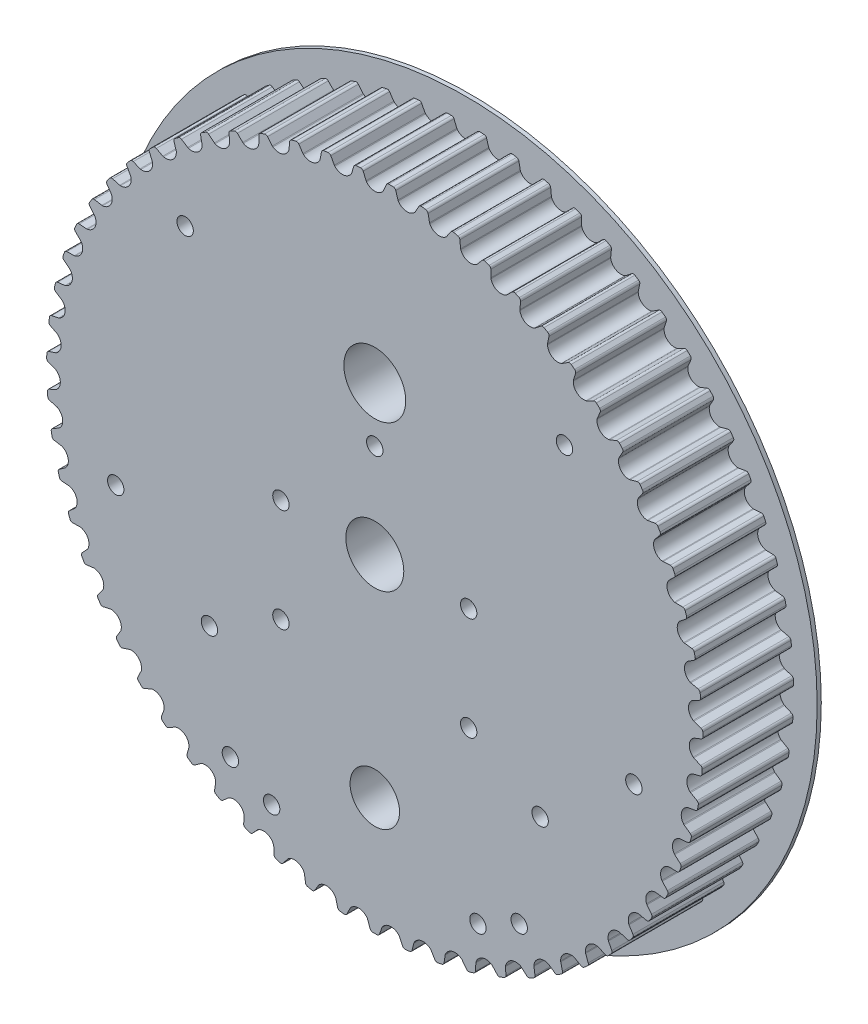
SolidWorks part; units mm, degrees
material "PETG"
ref_plane "Front Plane" through (0, 0, 0) normal (0, 0, 1) x (1, 0, 0)
ref_plane "Top Plane" through (0, 0, 0) normal (0, 1, 0) x (1, 0, 0)
ref_plane "Right Plane" through (0, 0, 0) normal (1, 0, 0) x (0, 0, -1)
sketch "Sketch1" plane through (0, 0, 0) normal (0, 0, 1) x (1, 0, 0)
  line L0 (0, 0) -> (0, 50000) construction
  line L1 (0, 0) -> (3.9983, 80.1144) construction
  line L2 (0, 0) -> (-3.9983, 80.1144) construction
  line L3 (-2.1085, 77.3973) -> (-2.8064, 79.0584)
  line L4 (2.1085, 77.3973) -> (2.8064, 79.0584)
  line L5 (5.6082, 77.2226) -> (5.0793, 78.9449)
  line L6 (9.8043, 76.8027) -> (10.6641, 78.3861)
  line L7 (13.2692, 76.2805) -> (12.9144, 78.0469)
  line L8 (17.4027, 75.4449) -> (18.4158, 76.9348)
  line L9 (20.7984, 74.5802) -> (20.6212, 76.3732)
  line L10 (24.8281, 73.3372) -> (25.9846, 74.7188)
  line L11 (28.1208, 72.1388) -> (28.123, 73.9405)
  line L12 (32.0068, 70.5007) -> (33.295, 71.7603)
  line L13 (35.1638, 68.9804) -> (35.3454, 70.7729)
  line L14 (38.8673, 66.9635) -> (40.2746, 68.0886)
  line L15 (41.8573, 65.1364) -> (42.2164, 66.902)
  line L16 (45.3416, 62.7608) -> (46.8539, 63.7402)
  line L17 (48.1348, 60.6451) -> (48.6679, 62.3661)
  line L18 (51.3652, 57.9344) -> (52.9675, 58.7583)
  line L19 (53.9339, 55.551) -> (54.6358, 57.2105)
  line L20 (56.8784, 52.5322) -> (58.5548, 53.1925)
  line L21 (59.197, 49.9049) -> (60.0606, 51.4862)
  line L22 (61.8263, 46.6079) -> (63.5601, 47.098)
  line L23 (63.8717, 43.7628) -> (64.8885, 45.2502)
  line L24 (66.1597, 40.2204) -> (67.9337, 40.5354)
  line L25 (67.9117, 37.1858) -> (69.0715, 38.5646)
  line L26 (69.8356, 33.4331) -> (71.6321, 33.57)
  line L27 (71.2767, 30.2392) -> (72.5681, 31.4956)
  line L28 (72.8174, 26.3136) -> (74.6186, 26.2709)
  line L29 (73.9334, 22.992) -> (75.3434, 24.1137)
  line L30 (75.0756, 18.9326) -> (76.8636, 18.7107)
  line L31 (75.8553, 15.5164) -> (77.37, 16.4921)
  line L32 (76.5876, 11.3634) -> (78.3446, 10.9646)
  line L33 (77.0233, 7.8865) -> (78.6276, 8.7066)
  line L34 (77.3384, 3.6813) -> (79.047, 3.1095)
  line L35 (77.4258, 0.1783) -> (79.1038, 0.8345)
  line L36 (77.3206, -4.0374) -> (78.9638, -4.7765)
  line L37 (77.0588, -7.5317) -> (78.7938, -7.0458)
  line L38 (76.5344, -11.716) -> (78.0959, -12.615)
  line L39 (75.9259, -15.1668) -> (77.7007, -14.8561)
  line L40 (74.9876, -19.2782) -> (76.4517, -20.3281)
  line L41 (74.0385, -22.6513) -> (75.8354, -22.5188)
  line L42 (72.6954, -26.6487) -> (74.0478, -27.8393)
  line L43 (71.4153, -29.9106) -> (73.2164, -29.9577)
  line L44 (69.6808, -33.7544) -> (70.908, -35.0737)
  line L45 (68.0823, -36.8726) -> (69.8697, -37.0988)
  line L46 (65.9737, -40.5247) -> (67.0634, -41.9596)
  line L47 (64.0726, -43.4682) -> (65.8287, -43.8712)
  line L48 (61.6109, -46.8922) -> (62.5523, -48.4284)
  line L49 (59.4262, -49.6317) -> (61.1334, -50.2076)
  line L50 (56.6358, -52.7936) -> (57.4196, -54.416)
  line L51 (54.1892, -55.302) -> (55.8306, -56.0451)
  line L52 (51.0978, -58.1704) -> (51.7161, -59.8627)
  line L53 (48.4136, -60.4227) -> (49.9728, -61.3255)
  line L54 (45.052, -62.969) -> (45.4988, -64.7145)
  line L55 (42.1568, -64.9429) -> (43.6185, -65.9965)
  line L56 (38.5585, -67.1418) -> (38.8292, -68.9231)
  line L57 (35.4811, -68.8177) -> (36.8306, -70.0115)
  line L58 (31.6817, -70.6474) -> (31.7737, -72.4468)
  line L59 (28.4528, -72.0085) -> (29.6767, -73.3307)
  line L60 (24.49, -73.4508) -> (24.4024, -75.2504)
  line L61 (21.1417, -74.4836) -> (22.2278, -75.9212)
  line L62 (17.055, -75.5242) -> (16.7887, -77.3062)
  line L63 (13.6204, -76.2185) -> (14.5581, -77.7571)
  line L64 (9.4505, -76.8471) -> (9.008, -78.5936)
  line L65 (5.9638, -77.1959) -> (6.7436, -78.8202)
  line L66 (1.752, -77.4061) -> (1.1379, -79.1)
  line L67 (-1.752, -77.4061) -> (-1.1379, -79.1)
  line L68 (-5.9638, -77.1959) -> (-6.7436, -78.8202)
  line L69 (-9.4505, -76.8471) -> (-9.008, -78.5936)
  line L70 (-13.6204, -76.2185) -> (-14.5581, -77.7571)
  line L71 (-17.055, -75.5242) -> (-16.7887, -77.3062)
  line L72 (-21.1417, -74.4836) -> (-22.2278, -75.9212)
  line L73 (-24.49, -73.4508) -> (-24.4024, -75.2504)
  line L74 (-28.4528, -72.0085) -> (-29.6767, -73.3307)
  line L75 (-31.6817, -70.6474) -> (-31.7737, -72.4468)
  line L76 (-35.4811, -68.8177) -> (-36.8306, -70.0115)
  line L77 (-38.5585, -67.1418) -> (-38.8292, -68.9231)
  line L78 (-42.1568, -64.9429) -> (-43.6185, -65.9965)
  line L79 (-45.052, -62.969) -> (-45.4988, -64.7145)
  line L80 (-48.4136, -60.4227) -> (-49.9728, -61.3255)
  line L81 (-51.0978, -58.1704) -> (-51.7161, -59.8627)
  line L82 (-54.1892, -55.302) -> (-55.8306, -56.0451)
  line L83 (-56.6358, -52.7936) -> (-57.4196, -54.416)
  line L84 (-59.4262, -49.6317) -> (-61.1334, -50.2076)
  line L85 (-61.6109, -46.8922) -> (-62.5523, -48.4284)
  line L86 (-64.0726, -43.4682) -> (-65.8287, -43.8712)
  line L87 (-65.9737, -40.5247) -> (-67.0634, -41.9596)
  line L88 (-68.0823, -36.8726) -> (-69.8697, -37.0988)
  line L89 (-69.6808, -33.7544) -> (-70.908, -35.0737)
  line L90 (-71.4153, -29.9106) -> (-73.2164, -29.9577)
  line L91 (-72.6954, -26.6487) -> (-74.0478, -27.8393)
  line L92 (-74.0385, -22.6513) -> (-75.8354, -22.5188)
  line L93 (-74.9876, -19.2782) -> (-76.4517, -20.3281)
  line L94 (-75.9259, -15.1668) -> (-77.7007, -14.8561)
  line L95 (-76.5344, -11.716) -> (-78.0959, -12.615)
  line L96 (-77.0588, -7.5317) -> (-78.7938, -7.0458)
  line L97 (-77.3206, -4.0374) -> (-78.9638, -4.7765)
  line L98 (-77.4258, 0.1783) -> (-79.1038, 0.8345)
  line L99 (-77.3384, 3.6813) -> (-79.047, 3.1095)
  line L100 (-77.0233, 7.8865) -> (-78.6276, 8.7066)
  line L101 (-76.5876, 11.3634) -> (-78.3446, 10.9646)
  line L102 (-75.8553, 15.5164) -> (-77.37, 16.4921)
  line L103 (-75.0756, 18.9326) -> (-76.8636, 18.7107)
  line L104 (-73.9334, 22.992) -> (-75.3434, 24.1137)
  line L105 (-72.8174, 26.3136) -> (-74.6186, 26.2709)
  line L106 (-71.2767, 30.2392) -> (-72.5681, 31.4956)
  line L107 (-69.8356, 33.4331) -> (-71.6321, 33.57)
  line L108 (-67.9117, 37.1858) -> (-69.0715, 38.5646)
  line L109 (-66.1597, 40.2204) -> (-67.9337, 40.5354)
  line L110 (-63.8717, 43.7628) -> (-64.8885, 45.2502)
  line L111 (-61.8263, 46.6079) -> (-63.5601, 47.098)
  line L112 (-59.197, 49.9049) -> (-60.0606, 51.4862)
  line L113 (-56.8784, 52.5322) -> (-58.5548, 53.1925)
  line L114 (-53.9339, 55.551) -> (-54.6358, 57.2105)
  line L115 (-51.3652, 57.9344) -> (-52.9675, 58.7583)
  line L116 (-48.1348, 60.6451) -> (-48.6679, 62.3661)
  line L117 (-45.3416, 62.7608) -> (-46.8539, 63.7402)
  line L118 (-41.8573, 65.1364) -> (-42.2164, 66.902)
  line L119 (-38.8673, 66.9635) -> (-40.2746, 68.0886)
  line L120 (-35.1638, 68.9804) -> (-35.3454, 70.7729)
  line L121 (-32.0068, 70.5007) -> (-33.295, 71.7603)
  line L122 (-28.1208, 72.1388) -> (-28.123, 73.9405)
  line L123 (0, 0) -> (2.0086, 77.226) construction
  line L124 (-24.8281, 73.3372) -> (-25.9846, 74.7188)
  line L125 (-20.7984, 74.5802) -> (-20.6212, 76.3732)
  line L126 (-17.4027, 75.4449) -> (-18.4158, 76.9348)
  line L127 (-13.2692, 76.2805) -> (-12.9144, 78.0469)
  line L128 (-9.8043, 76.8027) -> (-10.6641, 78.3861)
  line L129 (-5.6082, 77.2226) -> (-5.0793, 78.9449)
  circle A0 centre (0, 0) radius 80.2141 construction
  circle A317 centre (0, 0) radius 79.53 construction
  arc A318 (-2.0086, 77.226) -> (2.0086, 77.226) centre (0, 78.7807) ccw
  arc A319 (-2.0086, 77.226) -> (-2.1085, 77.3973) centre (-1.406, 77.6924) cw
  arc A320 (-2.8064, 79.0584) -> (-3.4334, 79.4559) centre (-3.4054, 78.8067) ccw
  arc A321 (-3.4334, 79.4559) -> (-3.9642, 79.4311) centre (0, 0) ccw
  arc A322 (3.4334, 79.4559) -> (3.9642, 79.4311) centre (0, 0) cw
  arc A323 (2.8064, 79.0584) -> (3.4334, 79.4559) centre (3.4054, 78.8067) cw
  arc A324 (2.0086, 77.226) -> (2.1085, 77.3973) centre (1.406, 77.6924) ccw
  arc A325 (4.4949, 79.4029) -> (3.9642, 79.4311) centre (0, 0) ccw
  arc A326 (5.0793, 78.9449) -> (4.4949, 79.4029) centre (4.4582, 78.7542) ccw
  arc A327 (5.6906, 77.0422) -> (9.6878, 76.6422) centre (7.844, 78.3892) ccw
  arc A328 (5.6906, 77.0422) -> (5.6082, 77.2226) centre (6.3366, 77.4463) cw
  arc A329 (9.6878, 76.6422) -> (9.8043, 76.8027) centre (9.1347, 77.1663) ccw
  arc A330 (10.6641, 78.3861) -> (11.3276, 78.7192) centre (11.2351, 78.0761) cw
  arc A331 (11.3276, 78.7192) -> (11.8533, 78.6417) centre (0, 0) cw
  arc A332 (12.3785, 78.5608) -> (11.8533, 78.6417) centre (0, 0) ccw
  arc A333 (12.9144, 78.0469) -> (12.3785, 78.5608) centre (12.2774, 77.919) ccw
  arc A334 (13.3333, 76.0928) -> (17.2708, 75.2968) centre (15.6101, 77.2187) ccw
  arc A335 (13.3333, 76.0928) -> (13.2692, 76.2805) centre (14.0163, 76.4305) cw
  arc A336 (17.2708, 75.2968) -> (17.4027, 75.4449) centre (16.7726, 75.8733) ccw
  arc A337 (18.4158, 76.9348) -> (19.1092, 77.2001) centre (18.9531, 76.5694) cw
  arc A338 (19.1092, 77.2001) -> (19.6246, 77.0707) centre (0, 0) cw
  arc A339 (20.1391, 76.9379) -> (19.6246, 77.0707) centre (0, 0) ccw
  arc A340 (20.6212, 76.3732) -> (20.1391, 76.9379) centre (19.9746, 76.3093) ccw
  arc A341 (20.8434, 74.3871) -> (24.6821, 73.203) centre (23.221, 75.2807) ccw
  arc A342 (20.8434, 74.3871) -> (20.7984, 74.5802) centre (21.5567, 74.6552) cw
  arc A343 (24.6821, 73.203) -> (24.8281, 73.3372) centre (24.2438, 73.8263) ccw
  arc A344 (25.9846, 74.7188) -> (26.7009, 74.9138) centre (26.4828, 74.3018) cw
  arc A345 (26.7009, 74.9138) -> (27.2009, 74.7338) centre (0, 0) cw
  arc A346 (27.6996, 74.5503) -> (27.2009, 74.7338) centre (0, 0) ccw
  arc A347 (28.123, 73.9405) -> (27.6996, 74.5503) centre (27.4733, 73.9413) ccw
  arc A348 (28.1464, 71.9421) -> (31.8481, 70.3817) centre (30.6012, 72.5945) ccw
  arc A349 (28.1464, 71.9421) -> (28.1208, 72.1388) centre (28.8828, 72.1378) cw
  arc A350 (31.8481, 70.3817) -> (32.0068, 70.5007) centre (31.474, 71.0455) ccw
  arc A351 (33.295, 71.7603) -> (34.0272, 71.883) centre (33.7493, 71.2958) cw
  arc A352 (34.0272, 71.883) -> (34.5068, 71.6541) centre (0, 0) cw
  arc A353 (34.9848, 71.4219) -> (34.5068, 71.6541) centre (0, 0) ccw
  arc A354 (35.3454, 70.7729) -> (34.9848, 71.4219) centre (34.699, 70.8384) ccw
  arc A355 (35.1696, 68.7821) -> (38.6976, 66.8609) centre (37.6772, 69.1869) ccw
  arc A356 (35.1696, 68.7821) -> (35.1638, 68.9804) centre (35.9219, 68.9036) cw
  arc A357 (38.6976, 66.8609) -> (38.8673, 66.9635) centre (38.3915, 67.5587) ccw
  arc A358 (40.2746, 68.0886) -> (41.0154, 68.1378) centre (40.6803, 67.5811) cw
  arc A359 (41.0154, 68.1378) -> (41.4697, 67.8622) centre (0, 0) cw
  arc A360 (41.9222, 67.5836) -> (41.4697, 67.8622) centre (0, 0) ccw
  arc A361 (42.2164, 66.902) -> (41.9222, 67.5836) centre (41.5798, 67.0315) ccw
  arc A362 (41.8434, 64.9386) -> (45.1625, 62.6756) centre (44.3787, 65.0917) ccw
  arc A363 (41.8434, 64.9386) -> (41.8573, 65.1364) centre (42.604, 64.9845) cw
  arc A364 (45.1625, 62.6756) -> (45.3416, 62.7608) centre (44.9274, 63.4004) ccw
  arc A365 (46.8539, 63.7402) -> (47.5959, 63.7154) centre (47.2071, 63.1949) cw
  arc A366 (47.5959, 63.7154) -> (48.0206, 63.3959) centre (0, 0) cw
  arc A367 (48.4431, 63.0737) -> (48.0206, 63.3959) centre (0, 0) ccw
  arc A368 (48.6679, 62.3661) -> (48.4431, 63.0737) centre (48.0473, 62.5584) ccw
  arc A369 (48.1012, 60.4496) -> (51.1786, 57.8674) centre (50.6393, 60.3495) ccw
  arc A370 (48.1012, 60.4496) -> (48.1348, 60.6451) centre (48.8626, 60.4196) cw
  arc A371 (51.1786, 57.8674) -> (51.3652, 57.9344) centre (51.0168, 58.6121) ccw
  arc A372 (52.9675, 58.7583) -> (53.7034, 58.6597) centre (53.2647, 58.1805) cw
  arc A373 (53.7034, 58.6597) -> (54.0941, 58.2996) centre (0, 0) cw
  arc A374 (54.4825, 57.9369) -> (54.0941, 58.2996) centre (0, 0) ccw
  arc A375 (54.6358, 57.2105) -> (54.4825, 57.9369) centre (54.0374, 57.4636) ccw
  arc A376 (53.881, 55.3599) -> (56.686, 52.4841) centre (56.3965, 55.0076) ccw
  arc A377 (53.881, 55.3599) -> (53.9339, 55.551) centre (54.6357, 55.2542) cw
  arc A378 (56.686, 52.4841) -> (56.8784, 52.5322) centre (56.5991, 53.2412) ccw
  arc A379 (58.5548, 53.1925) -> (59.2772, 53.0211) centre (58.7929, 52.588) cw
  arc A380 (59.2772, 53.0211) -> (59.6301, 52.6239) centre (0, 0) cw
  arc A381 (59.9804, 52.2243) -> (59.6301, 52.6239) centre (0, 0) ccw
  arc A382 (60.0606, 51.4862) -> (59.9804, 52.2243) centre (59.4904, 51.7976) ccw
  arc A383 (59.1254, 49.72) -> (61.63, 46.5792) centre (61.5932, 49.119) ccw
  arc A384 (59.1254, 49.72) -> (59.197, 49.9049) centre (59.8657, 49.5397) cw
  arc A385 (61.63, 46.5792) -> (61.8263, 46.6079) centre (61.619, 47.3411) ccw
  arc A386 (63.5601, 47.098) -> (64.2618, 46.8555) centre (63.7368, 46.4728) cw
  arc A387 (64.2618, 46.8555) -> (64.5734, 46.4251) centre (0, 0) cw
  arc A388 (64.8822, 45.9926) -> (64.5734, 46.4251) centre (0, 0) ccw
  arc A389 (64.8885, 45.2502) -> (64.8822, 45.9926) centre (64.3521, 45.6169) ccw
  arc A390 (63.7821, 43.5859) -> (65.9616, 40.2114) centre (66.1778, 42.7422) ccw
  arc A391 (63.7821, 43.5859) -> (63.8717, 43.7628) centre (64.5008, 43.3328) cw
  arc A392 (65.9616, 40.2114) -> (66.1597, 40.2204) centre (66.0264, 40.9706) ccw
  arc A393 (67.9337, 40.5354) -> (68.6078, 40.2243) centre (68.0473, 39.8957) cw
  arc A394 (68.6078, 40.2243) -> (68.875, 39.765) centre (0, 0) cw
  arc A395 (69.1392, 39.3039) -> (68.875, 39.765) centre (0, 0) ccw
  arc A396 (69.0715, 38.5646) -> (69.1392, 39.3039) centre (68.5743, 38.9828) ccw
  arc A397 (67.8049, 37.0187) -> (69.6375, 33.4439) centre (70.1047, 35.9406) ccw
  arc A398 (67.8049, 37.0187) -> (67.9117, 37.1858) centre (68.4948, 36.6953) cw
  arc A399 (69.6375, 33.4439) -> (69.8356, 33.4331) centre (69.7777, 34.1929) ccw
  arc A400 (71.6321, 33.57) -> (72.2719, 33.1933) centre (71.6815, 32.9221) cw
  arc A401 (72.2719, 33.1933) -> (72.4921, 32.7097) centre (0, 0) cw
  arc A402 (72.709, 32.2246) -> (72.4921, 32.7097) centre (0, 0) ccw
  arc A403 (72.5681, 31.4956) -> (72.709, 32.2246) centre (72.115, 31.9613) ccw
  arc A404 (71.1538, 30.0836) -> (72.6214, 26.3441) centre (73.3349, 28.7818) ccw
  arc A405 (71.1538, 30.0836) -> (71.2767, 30.2392) centre (71.8081, 29.693) cw
  arc A406 (72.6214, 26.3441) -> (72.8174, 26.3136) centre (72.8355, 27.0754) ccw
  arc A407 (74.6186, 26.2709) -> (75.2177, 25.8324) centre (74.6032, 25.6214) cw
  arc A408 (75.2177, 25.8324) -> (75.3887, 25.3292) centre (0, 0) cw
  arc A409 (75.5562, 24.825) -> (75.3887, 25.3292) centre (0, 0) ccw
  arc A410 (75.3434, 24.1137) -> (75.5562, 24.825) centre (74.939, 24.6222) ccw
  arc A411 (73.7956, 22.8494) -> (74.8836, 18.9824) centre (75.8362, 21.337) ccw
  arc A412 (73.7956, 22.8494) -> (73.9334, 22.992) centre (74.4078, 22.3957) cw
  arc A413 (74.8836, 18.9824) -> (75.0756, 18.9326) centre (75.1694, 19.6888) ccw
  arc A414 (76.8636, 18.7107) -> (77.416, 18.2148) centre (76.7836, 18.066) cw
  arc A415 (77.416, 18.2148) -> (77.536, 17.6971) centre (0, 0) cw
  arc A416 (77.6525, 17.1786) -> (77.536, 17.6971) centre (0, 0) ccw
  arc A417 (77.37, 16.4921) -> (77.6525, 17.1786) centre (77.0181, 17.0383) ccw
  arc A418 (75.7039, 15.3882) -> (76.4015, 11.4321) centre (77.5838, 13.6801) ccw
  arc A419 (75.7039, 15.3882) -> (75.8553, 15.5164) centre (76.2679, 14.8758) cw
  arc A420 (76.4015, 11.4321) -> (76.5876, 11.3634) centre (76.7562, 12.1065) ccw
  arc A421 (78.3446, 10.9646) -> (78.8449, 10.4161) centre (78.2008, 10.331) cw
  arc A422 (78.8449, 10.4161) -> (78.9128, 9.8891) centre (0, 0) cw
  arc A423 (78.9771, 9.3616) -> (78.9128, 9.8891) centre (0, 0) ccw
  arc A424 (78.6276, 8.7066) -> (78.9771, 9.3616) centre (78.3319, 9.2851) ccw
  arc A425 (76.8599, 7.7741) -> (77.1601, 3.7681) centre (78.5604, 5.8873) ccw
  arc A426 (76.8599, 7.7741) -> (77.0233, 7.8865) centre (77.3701, 7.208) cw
  arc A427 (77.1601, 3.7681) -> (77.3384, 3.6813) centre (77.5802, 4.4039) ccw
  arc A428 (79.047, 3.1095) -> (79.4903, 2.5139) centre (78.8409, 2.4934) cw
  arc A429 (79.4903, 2.5139) -> (79.5053, 1.9827) centre (0, 0) cw
  arc A430 (79.5168, 1.4515) -> (79.5053, 1.9827) centre (0, 0) ccw
  arc A431 (79.1038, 0.8345) -> (79.5168, 1.4515) centre (78.8671, 1.4396) ccw
  arc A432 (77.252, 0.0827) -> (77.1519, -3.9333) centre (78.7562, -1.9641) ccw
  arc A433 (77.252, 0.0827) -> (77.4258, 0.1783) centre (77.7033, -0.5314) cw
  arc A434 (77.1519, -3.9333) -> (77.3206, -4.0374) centre (77.6332, -3.3425) ccw
  arc A435 (78.9638, -4.7765) -> (79.3456, -5.4133) centre (78.6973, -5.369) cw
  arc A436 (79.3456, -5.4133) -> (79.3076, -5.9433) centre (0, 0) cw
  arc A437 (79.2661, -6.4731) -> (79.3076, -5.9433) centre (0, 0) ccw
  arc A438 (78.7938, -7.0458) -> (79.2661, -6.4731) centre (78.6186, -6.4202) ccw
  arc A439 (76.8764, -7.6096) -> (76.3769, -11.5956) centre (78.1693, -9.7959) ccw
  arc A440 (76.8764, -7.6096) -> (77.0588, -7.5317) centre (77.2643, -8.2655) cw
  arc A441 (76.3769, -11.5956) -> (76.5344, -11.716) centre (76.9146, -11.0557) ccw
  arc A442 (78.0959, -12.615) -> (78.4123, -13.2866) centre (77.7717, -13.1781) cw
  arc A443 (78.4123, -13.2866) -> (78.3218, -13.8102) centre (0, 0) cw
  arc A444 (78.2277, -14.3332) -> (78.3218, -13.8102) centre (0, 0) ccw
  arc A445 (77.7007, -14.8561) -> (78.2277, -14.3332) centre (77.5887, -14.2161) ccw
  arc A446 (75.7367, -15.2262) -> (74.8428, -19.1426) centre (76.8055, -17.5304) ccw
  arc A447 (75.7367, -15.2262) -> (75.9259, -15.1668) centre (76.0573, -15.9174) cw
  arc A448 (74.8428, -19.1426) -> (74.9876, -19.2782) centre (75.4316, -18.6589) ccw
  arc A449 (76.4517, -20.3281) -> (76.6997, -21.0279) centre (76.0731, -20.8561) cw
  arc A450 (76.6997, -21.0279) -> (76.5575, -21.5399) centre (0, 0) cw
  arc A451 (76.4119, -22.051) -> (76.5575, -21.5399) centre (0, 0) ccw
  arc A452 (75.8354, -22.5188) -> (76.4119, -22.051) centre (75.7876, -21.8708) ccw
  arc A453 (73.8443, -22.6914) -> (72.5649, -26.4994) centre (74.6784, -25.0906) ccw
  arc A454 (73.8443, -22.6914) -> (74.0385, -22.6513) centre (74.0945, -23.4112) cw
  arc A455 (72.5649, -26.4994) -> (72.6954, -26.6487) centre (73.1989, -26.0768) ccw
  arc A456 (74.0478, -27.8393) -> (74.2249, -28.5603) centre (73.6185, -28.3269) cw
  arc A457 (74.2249, -28.5603) -> (74.0324, -29.0556) centre (0, 0) cw
  arc A458 (73.8366, -29.5496) -> (74.0324, -29.0556) centre (0, 0) ccw
  arc A459 (73.2164, -29.9577) -> (73.8366, -29.5496) centre (73.2334, -29.3082) ccw
  arc A460 (71.218, -29.9312) -> (69.5658, -33.5929) centre (71.8091, -32.4015) ccw
  arc A461 (71.218, -29.9312) -> (71.4153, -29.9106) centre (71.3953, -30.6723) cw
  arc A462 (69.5658, -33.5929) -> (69.6808, -33.7544) centre (70.2388, -33.2355) ccw
  arc A463 (70.908, -35.0737) -> (71.0123, -35.8088) centre (70.4322, -35.5162) cw
  arc A464 (71.0123, -35.8088) -> (70.7715, -36.2824) centre (0, 0) cw
  arc A465 (70.5275, -36.7545) -> (70.7715, -36.2824) centre (0, 0) ccw
  arc A466 (69.8697, -37.0988) -> (70.5275, -36.7545) centre (69.9513, -36.4542) ccw
  arc A467 (67.8839, -36.8735) -> (65.8754, -40.3525) centre (68.2261, -39.3903) ccw
  arc A468 (67.8839, -36.8735) -> (68.0823, -36.8726) centre (67.9866, -37.6286) cw
  arc A469 (65.8754, -40.3525) -> (65.9737, -40.5247) centre (66.5806, -40.0638) ccw
  arc A470 (67.0634, -41.9596) -> (67.0941, -42.7014) centre (66.5459, -42.3525) cw
  arc A471 (67.0941, -42.7014) -> (66.8073, -43.1487) centre (0, 0) cw
  arc A472 (66.5175, -43.5941) -> (66.8073, -43.1487) centre (0, 0) ccw
  arc A473 (65.8287, -43.8712) -> (66.5175, -43.5941) centre (65.974, -43.238) ccw
  arc A474 (63.8752, -43.4493) -> (61.5302, -46.711) centre (63.965, -45.9877) ccw
  arc A475 (63.8752, -43.4493) -> (64.0726, -43.4682) centre (63.9021, -44.2108) cw
  arc A476 (61.5302, -46.711) -> (61.6109, -46.8922) centre (62.2607, -46.494) ccw
  arc A477 (62.5523, -48.4284) -> (62.509, -49.1696) centre (61.9983, -48.7679) cw
  arc A478 (62.509, -49.1696) -> (62.1791, -49.5861) centre (0, 0) cw
  arc A479 (61.8464, -50.0005) -> (62.1791, -49.5861) centre (0, 0) ccw
  arc A480 (61.1334, -50.2076) -> (61.8464, -50.0005) centre (61.3411, -49.592) ccw
  arc A481 (59.2316, -49.5933) -> (56.5735, -52.6053) centre (59.0683, -52.1281) ccw
  arc A482 (59.2316, -49.5933) -> (59.4262, -49.6317) centre (59.1826, -50.3538) cw
  arc A483 (56.5735, -52.6053) -> (56.6358, -52.7936) centre (57.322, -52.4621) ccw
  arc A484 (57.4196, -54.416) -> (57.3027, -55.1491) centre (56.8345, -54.6986) cw
  arc A485 (57.3027, -55.1491) -> (56.9329, -55.5308) centre (0, 0) cw
  arc A486 (56.5606, -55.9099) -> (56.9329, -55.5308) centre (0, 0) ccw
  arc A487 (55.8306, -56.0451) -> (56.5606, -55.9099) centre (56.0985, -55.4532) ccw
  arc A488 (53.9994, -55.2445) -> (51.0546, -57.9768) centre (53.5845, -57.7503) ccw
  arc A489 (53.9994, -55.2445) -> (54.1892, -55.302) centre (53.8749, -55.9962) cw
  arc A490 (51.0546, -57.9768) -> (51.0978, -58.1704) centre (51.8136, -57.9089) ccw
  arc A491 (51.7161, -59.8627) -> (51.5268, -60.5806) centre (51.1059, -60.0857) cw
  arc A492 (51.5268, -60.5806) -> (51.1209, -60.9235) centre (0, 0) cw
  arc A493 (50.7127, -61.2637) -> (51.1209, -60.9235) centre (0, 0) ccw
  arc A494 (49.9728, -61.3255) -> (50.7127, -61.2637) centre (50.2984, -60.7632) ccw
  arc A495 (48.2305, -60.3465) -> (45.0283, -62.7721) centre (47.5681, -62.7987) ccw
  arc A496 (48.2305, -60.3465) -> (48.4136, -60.4227) centre (48.0318, -61.0822) cw
  arc A497 (45.0283, -62.7721) -> (45.052, -62.969) centre (45.7902, -62.7801) ccw
  arc A498 (45.4988, -64.7145) -> (45.2389, -65.41) centre (44.8693, -64.8756) cw
  arc A499 (45.2389, -65.41) -> (44.8008, -65.7108) centre (0, 0) cw
  arc A500 (44.3608, -66.0086) -> (44.8008, -65.7108) centre (0, 0) ccw
  arc A501 (43.6185, -65.9965) -> (44.3608, -66.0086) centre (43.9984, -65.4694) ccw
  arc A502 (41.9822, -64.8489) -> (38.5544, -66.9436) centre (41.079, -67.2229) ccw
  arc A503 (41.9822, -64.8489) -> (42.1568, -64.9429) centre (41.7113, -65.5611) cw
  arc A504 (38.5544, -66.9436) -> (38.5585, -67.1418) centre (39.3118, -67.0273) ccw
  arc A505 (38.8292, -68.9231) -> (38.5014, -69.5893) centre (38.1868, -69.0208) cw
  arc A506 (38.5014, -69.5893) -> (38.0355, -69.845) centre (0, 0) cw
  arc A507 (37.568, -70.0975) -> (38.0355, -69.845) centre (0, 0) ccw
  arc A508 (36.8306, -70.0115) -> (37.568, -70.0975) centre (37.2611, -69.5249) ccw
  arc A509 (35.3168, -68.7067) -> (31.6974, -70.4497) centre (34.1817, -70.979) ccw
  arc A510 (35.3168, -68.7067) -> (35.4811, -68.8177) centre (34.9762, -69.3884) cw
  arc A511 (31.6974, -70.4497) -> (31.6817, -70.6474) centre (32.4427, -70.6085) ccw
  arc A512 (31.7737, -72.4468) -> (31.3812, -73.077) centre (31.1248, -72.48) cw
  arc A513 (31.3812, -73.077) -> (30.8922, -73.285) centre (0, 0) cw
  arc A514 (30.4019, -73.4898) -> (30.8922, -73.285) centre (0, 0) ccw
  arc A515 (29.6767, -73.3307) -> (30.4019, -73.4898) centre (30.1535, -72.8894) ccw
  arc A516 (28.3003, -71.8817) -> (24.5254, -73.2556) centre (26.9446, -74.0296) ccw
  arc A517 (28.3003, -71.8817) -> (28.4528, -72.0085) centre (27.8936, -72.5261) cw
  arc A518 (24.5254, -73.2556) -> (24.49, -73.4508) centre (25.2511, -73.4878) ccw
  arc A519 (24.4024, -75.2504) -> (23.9491, -75.8384) centre (23.7535, -75.2188) cw
  arc A520 (23.9491, -75.8384) -> (23.4419, -75.9967) centre (0, 0) cw
  arc A521 (22.9336, -76.1516) -> (23.4419, -75.9967) centre (0, 0) ccw
  arc A522 (22.2278, -75.9212) -> (22.9336, -76.1516) centre (22.7462, -75.5295) ccw
  arc A523 (21.0026, -74.3423) -> (17.1096, -75.3336) centre (19.4397, -76.3446) ccw
  arc A524 (21.0026, -74.3423) -> (21.1417, -74.4836) centre (20.5337, -74.943) cw
  arc A525 (17.1096, -75.3336) -> (17.055, -75.5242) centre (17.8086, -75.6369) ccw
  arc A526 (16.7887, -77.3062) -> (16.2791, -77.8461) centre (16.1461, -77.2101) cw
  arc A527 (16.2791, -77.8461) -> (15.7586, -77.9531) centre (0, 0) cw
  arc A528 (15.2374, -78.0567) -> (15.7586, -77.9531) centre (0, 0) ccw
  arc A529 (14.5581, -77.7571) -> (15.2374, -78.0567) centre (15.1129, -77.419) ccw
  arc A530 (13.4961, -76.0641) -> (9.5238, -76.6628) centre (11.7417, -77.9008) ccw
  arc A531 (13.4961, -76.0641) -> (13.6204, -76.2185) centre (12.9698, -76.6151) cw
  arc A532 (9.5238, -76.6628) -> (9.4505, -76.8471) centre (10.1891, -77.0342) ccw
  arc A533 (9.008, -78.5936) -> (8.4472, -79.0801) centre (8.3782, -78.4341) cw
  arc A534 (8.4472, -79.0801) -> (7.9186, -79.1348) centre (0, 0) cw
  arc A535 (7.3897, -79.1859) -> (7.9186, -79.1348) centre (0, 0) ccw
  arc A536 (6.7436, -78.8202) -> (7.3897, -79.1859) centre (7.3293, -78.539) ccw
  arc A537 (5.8555, -77.0298) -> (1.8433, -77.2301) centre (3.9269, -78.6828) ccw
  arc A538 (5.8555, -77.0298) -> (5.9638, -77.1959) centre (5.2769, -77.5257) cw
  arc A539 (1.8433, -77.2301) -> (1.752, -77.4061) centre (2.4684, -77.6659) ccw
  arc A540 (1.1379, -79.1) -> (0.5314, -79.5282) centre (0.527, -78.8785) cw
  arc A541 (0.5314, -79.5282) -> (0, -79.53) centre (0, 0) cw
  arc A542 (-0.5314, -79.5282) -> (0, -79.53) centre (0, 0) ccw
  arc A543 (-1.1379, -79.1) -> (-0.5314, -79.5282) centre (-0.527, -78.8785) ccw
  arc A544 (-1.8433, -77.2301) -> (-5.8555, -77.0298) centre (-3.9269, -78.6828) ccw
  arc A545 (-1.8433, -77.2301) -> (-1.752, -77.4061) centre (-2.4684, -77.6659) cw
  arc A546 (-5.8555, -77.0298) -> (-5.9638, -77.1959) centre (-5.2769, -77.5257) ccw
  arc A547 (-6.7436, -78.8202) -> (-7.3897, -79.1859) centre (-7.3293, -78.539) cw
  arc A548 (-7.3897, -79.1859) -> (-7.9186, -79.1348) centre (0, 0) cw
  arc A549 (-8.4472, -79.0801) -> (-7.9186, -79.1348) centre (0, 0) ccw
  arc A550 (-9.008, -78.5936) -> (-8.4472, -79.0801) centre (-8.3782, -78.4341) ccw
  arc A551 (-9.5238, -76.6628) -> (-13.4961, -76.0641) centre (-11.7417, -77.9008) ccw
  arc A552 (-9.5238, -76.6628) -> (-9.4505, -76.8471) centre (-10.1891, -77.0342) cw
  arc A553 (-13.4961, -76.0641) -> (-13.6204, -76.2185) centre (-12.9698, -76.6151) ccw
  arc A554 (-14.5581, -77.7571) -> (-15.2374, -78.0567) centre (-15.1129, -77.419) cw
  arc A555 (-15.2374, -78.0567) -> (-15.7586, -77.9531) centre (0, 0) cw
  arc A556 (-16.2791, -77.8461) -> (-15.7586, -77.9531) centre (0, 0) ccw
  arc A557 (-16.7887, -77.3062) -> (-16.2791, -77.8461) centre (-16.1461, -77.2101) ccw
  arc A558 (-17.1096, -75.3336) -> (-21.0026, -74.3423) centre (-19.4397, -76.3446) ccw
  arc A559 (-17.1096, -75.3336) -> (-17.055, -75.5242) centre (-17.8086, -75.6369) cw
  arc A560 (-21.0026, -74.3423) -> (-21.1417, -74.4836) centre (-20.5337, -74.943) ccw
  arc A561 (-22.2278, -75.9212) -> (-22.9336, -76.1516) centre (-22.7462, -75.5295) cw
  arc A562 (-22.9336, -76.1516) -> (-23.4419, -75.9967) centre (0, 0) cw
  arc A563 (-23.9491, -75.8384) -> (-23.4419, -75.9967) centre (0, 0) ccw
  arc A564 (-24.4024, -75.2504) -> (-23.9491, -75.8384) centre (-23.7535, -75.2188) ccw
  arc A565 (-24.5254, -73.2556) -> (-28.3003, -71.8817) centre (-26.9446, -74.0296) ccw
  arc A566 (-24.5254, -73.2556) -> (-24.49, -73.4508) centre (-25.2511, -73.4878) cw
  arc A567 (-28.3003, -71.8817) -> (-28.4528, -72.0085) centre (-27.8936, -72.5261) ccw
  arc A568 (-29.6767, -73.3307) -> (-30.4019, -73.4898) centre (-30.1535, -72.8894) cw
  arc A569 (-30.4019, -73.4898) -> (-30.8922, -73.285) centre (0, 0) cw
  arc A570 (-31.3812, -73.077) -> (-30.8922, -73.285) centre (0, 0) ccw
  arc A571 (-31.7737, -72.4468) -> (-31.3812, -73.077) centre (-31.1248, -72.48) ccw
  arc A572 (-31.6974, -70.4497) -> (-35.3168, -68.7067) centre (-34.1817, -70.979) ccw
  arc A573 (-31.6974, -70.4497) -> (-31.6817, -70.6474) centre (-32.4427, -70.6085) cw
  arc A574 (-35.3168, -68.7067) -> (-35.4811, -68.8177) centre (-34.9762, -69.3884) ccw
  arc A575 (-36.8306, -70.0115) -> (-37.568, -70.0975) centre (-37.2611, -69.5249) cw
  arc A576 (-37.568, -70.0975) -> (-38.0355, -69.845) centre (0, 0) cw
  arc A577 (-38.5014, -69.5893) -> (-38.0355, -69.845) centre (0, 0) ccw
  arc A578 (-38.8292, -68.9231) -> (-38.5014, -69.5893) centre (-38.1868, -69.0208) ccw
  arc A579 (-38.5544, -66.9436) -> (-41.9822, -64.8489) centre (-41.079, -67.2229) ccw
  arc A580 (-38.5544, -66.9436) -> (-38.5585, -67.1418) centre (-39.3118, -67.0273) cw
  arc A581 (-41.9822, -64.8489) -> (-42.1568, -64.9429) centre (-41.7113, -65.5611) ccw
  arc A582 (-43.6185, -65.9965) -> (-44.3608, -66.0086) centre (-43.9984, -65.4694) cw
  arc A583 (-44.3608, -66.0086) -> (-44.8008, -65.7108) centre (0, 0) cw
  arc A584 (-45.2389, -65.41) -> (-44.8008, -65.7108) centre (0, 0) ccw
  arc A585 (-45.4988, -64.7145) -> (-45.2389, -65.41) centre (-44.8693, -64.8756) ccw
  arc A586 (-45.0283, -62.7721) -> (-48.2305, -60.3465) centre (-47.5681, -62.7987) ccw
  arc A587 (-45.0283, -62.7721) -> (-45.052, -62.969) centre (-45.7902, -62.7801) cw
  arc A588 (-48.2305, -60.3465) -> (-48.4136, -60.4227) centre (-48.0318, -61.0822) ccw
  arc A589 (-49.9728, -61.3255) -> (-50.7127, -61.2637) centre (-50.2984, -60.7632) cw
  arc A590 (-50.7127, -61.2637) -> (-51.1209, -60.9235) centre (0, 0) cw
  arc A591 (-51.5268, -60.5806) -> (-51.1209, -60.9235) centre (0, 0) ccw
  arc A592 (-51.7161, -59.8627) -> (-51.5268, -60.5806) centre (-51.1059, -60.0857) ccw
  arc A593 (-51.0546, -57.9768) -> (-53.9994, -55.2445) centre (-53.5845, -57.7503) ccw
  arc A594 (-51.0546, -57.9768) -> (-51.0978, -58.1704) centre (-51.8136, -57.9089) cw
  arc A595 (-53.9994, -55.2445) -> (-54.1892, -55.302) centre (-53.8749, -55.9962) ccw
  arc A596 (-55.8306, -56.0451) -> (-56.5606, -55.9099) centre (-56.0985, -55.4532) cw
  arc A597 (-56.5606, -55.9099) -> (-56.9329, -55.5308) centre (0, 0) cw
  arc A598 (-57.3027, -55.1491) -> (-56.9329, -55.5308) centre (0, 0) ccw
  arc A599 (-57.4196, -54.416) -> (-57.3027, -55.1491) centre (-56.8345, -54.6986) ccw
  arc A600 (-56.5735, -52.6053) -> (-59.2316, -49.5933) centre (-59.0683, -52.1281) ccw
  arc A601 (-56.5735, -52.6053) -> (-56.6358, -52.7936) centre (-57.322, -52.4621) cw
  arc A602 (-59.2316, -49.5933) -> (-59.4262, -49.6317) centre (-59.1826, -50.3538) ccw
  arc A603 (-61.1334, -50.2076) -> (-61.8464, -50.0005) centre (-61.3411, -49.592) cw
  arc A604 (-61.8464, -50.0005) -> (-62.1791, -49.5861) centre (0, 0) cw
  arc A605 (-62.509, -49.1696) -> (-62.1791, -49.5861) centre (0, 0) ccw
  arc A606 (-62.5523, -48.4284) -> (-62.509, -49.1696) centre (-61.9983, -48.7679) ccw
  arc A607 (-61.5302, -46.711) -> (-63.8752, -43.4493) centre (-63.965, -45.9877) ccw
  arc A608 (-61.5302, -46.711) -> (-61.6109, -46.8922) centre (-62.2607, -46.494) cw
  arc A609 (-63.8752, -43.4493) -> (-64.0726, -43.4682) centre (-63.9021, -44.2108) ccw
  arc A610 (-65.8287, -43.8712) -> (-66.5175, -43.5941) centre (-65.974, -43.238) cw
  arc A611 (-66.5175, -43.5941) -> (-66.8073, -43.1487) centre (0, 0) cw
  arc A612 (-67.0941, -42.7014) -> (-66.8073, -43.1487) centre (0, 0) ccw
  arc A613 (-67.0634, -41.9596) -> (-67.0941, -42.7014) centre (-66.5459, -42.3525) ccw
  arc A614 (-65.8754, -40.3525) -> (-67.8839, -36.8735) centre (-68.2261, -39.3904) ccw
  arc A615 (-65.8754, -40.3525) -> (-65.9737, -40.5247) centre (-66.5806, -40.0638) cw
  arc A616 (-67.8839, -36.8735) -> (-68.0823, -36.8726) centre (-67.9866, -37.6286) ccw
  arc A617 (-69.8697, -37.0988) -> (-70.5275, -36.7545) centre (-69.9513, -36.4542) cw
  arc A618 (-70.5275, -36.7545) -> (-70.7715, -36.2824) centre (0, 0) cw
  arc A619 (-71.0123, -35.8088) -> (-70.7715, -36.2824) centre (0, 0) ccw
  arc A620 (-70.908, -35.0737) -> (-71.0123, -35.8088) centre (-70.4322, -35.5162) ccw
  arc A621 (-69.5658, -33.5929) -> (-71.218, -29.9312) centre (-71.8091, -32.4015) ccw
  arc A622 (-69.5658, -33.5929) -> (-69.6808, -33.7544) centre (-70.2388, -33.2355) cw
  arc A623 (-71.218, -29.9312) -> (-71.4153, -29.9106) centre (-71.3953, -30.6723) ccw
  arc A624 (-73.2164, -29.9577) -> (-73.8366, -29.5496) centre (-73.2334, -29.3082) cw
  arc A625 (-73.8366, -29.5496) -> (-74.0324, -29.0556) centre (0, 0) cw
  arc A626 (-74.2249, -28.5603) -> (-74.0324, -29.0556) centre (0, 0) ccw
  arc A627 (-74.0478, -27.8393) -> (-74.2249, -28.5603) centre (-73.6185, -28.3269) ccw
  arc A628 (-72.5649, -26.4994) -> (-73.8443, -22.6914) centre (-74.6784, -25.0906) ccw
  arc A629 (-72.5649, -26.4994) -> (-72.6954, -26.6487) centre (-73.1989, -26.0768) cw
  arc A630 (-73.8443, -22.6914) -> (-74.0385, -22.6513) centre (-74.0945, -23.4112) ccw
  arc A631 (-75.8354, -22.5188) -> (-76.4119, -22.051) centre (-75.7876, -21.8708) cw
  arc A632 (-76.4119, -22.051) -> (-76.5575, -21.5399) centre (0, 0) cw
  arc A633 (-76.6997, -21.0279) -> (-76.5575, -21.5399) centre (0, 0) ccw
  arc A634 (-76.4517, -20.3281) -> (-76.6997, -21.0279) centre (-76.0731, -20.8561) ccw
  arc A635 (-74.8428, -19.1426) -> (-75.7367, -15.2262) centre (-76.8055, -17.5304) ccw
  arc A636 (-74.8428, -19.1426) -> (-74.9876, -19.2782) centre (-75.4316, -18.6589) cw
  arc A637 (-75.7367, -15.2262) -> (-75.9259, -15.1668) centre (-76.0573, -15.9174) ccw
  arc A638 (-77.7007, -14.8561) -> (-78.2277, -14.3332) centre (-77.5887, -14.2161) cw
  arc A639 (-78.2277, -14.3332) -> (-78.3218, -13.8102) centre (0, 0) cw
  arc A640 (-78.4123, -13.2866) -> (-78.3218, -13.8102) centre (0, 0) ccw
  arc A641 (-78.0959, -12.615) -> (-78.4123, -13.2866) centre (-77.7717, -13.1781) ccw
  arc A642 (-76.3769, -11.5956) -> (-76.8764, -7.6096) centre (-78.1693, -9.7959) ccw
  arc A643 (-76.3769, -11.5956) -> (-76.5344, -11.716) centre (-76.9146, -11.0557) cw
  arc A644 (-76.8764, -7.6096) -> (-77.0588, -7.5317) centre (-77.2643, -8.2655) ccw
  arc A645 (-78.7938, -7.0458) -> (-79.2661, -6.4731) centre (-78.6186, -6.4202) cw
  arc A646 (-79.2661, -6.4731) -> (-79.3076, -5.9433) centre (0, 0) cw
  arc A647 (-79.3456, -5.4133) -> (-79.3076, -5.9433) centre (0, 0) ccw
  arc A648 (-78.9638, -4.7765) -> (-79.3456, -5.4133) centre (-78.6973, -5.369) ccw
  arc A649 (-77.1519, -3.9333) -> (-77.252, 0.0827) centre (-78.7562, -1.9641) ccw
  arc A650 (-77.1519, -3.9333) -> (-77.3206, -4.0374) centre (-77.6332, -3.3425) cw
  arc A651 (-77.252, 0.0827) -> (-77.4258, 0.1783) centre (-77.7033, -0.5314) ccw
  arc A652 (-79.1038, 0.8345) -> (-79.5168, 1.4515) centre (-78.8671, 1.4396) cw
  arc A653 (-79.5168, 1.4515) -> (-79.5053, 1.9827) centre (0, 0) cw
  arc A654 (-79.4903, 2.5139) -> (-79.5053, 1.9827) centre (0, 0) ccw
  arc A655 (-79.047, 3.1095) -> (-79.4903, 2.5139) centre (-78.8409, 2.4934) ccw
  arc A656 (-77.1601, 3.7681) -> (-76.8599, 7.7741) centre (-78.5604, 5.8873) ccw
  arc A657 (-77.1601, 3.7681) -> (-77.3384, 3.6813) centre (-77.5802, 4.4039) cw
  arc A658 (-76.8599, 7.7741) -> (-77.0233, 7.8865) centre (-77.3701, 7.208) ccw
  arc A659 (-78.6276, 8.7066) -> (-78.9771, 9.3616) centre (-78.3319, 9.2851) cw
  arc A660 (-78.9771, 9.3616) -> (-78.9128, 9.8891) centre (0, 0) cw
  arc A661 (-78.8449, 10.4161) -> (-78.9128, 9.8891) centre (0, 0) ccw
  arc A662 (-78.3446, 10.9646) -> (-78.8449, 10.4161) centre (-78.2008, 10.331) ccw
  arc A663 (-76.4015, 11.4321) -> (-75.7039, 15.3882) centre (-77.5838, 13.6801) ccw
  arc A664 (-76.4015, 11.4321) -> (-76.5876, 11.3634) centre (-76.7562, 12.1065) cw
  arc A665 (-75.7039, 15.3882) -> (-75.8553, 15.5164) centre (-76.2679, 14.8758) ccw
  arc A666 (-77.37, 16.4921) -> (-77.6525, 17.1786) centre (-77.0181, 17.0383) cw
  arc A667 (-77.6525, 17.1786) -> (-77.536, 17.6971) centre (0, 0) cw
  arc A668 (-77.416, 18.2148) -> (-77.536, 17.6971) centre (0, 0) ccw
  arc A669 (-76.8636, 18.7107) -> (-77.416, 18.2148) centre (-76.7836, 18.066) ccw
  arc A670 (-74.8836, 18.9824) -> (-73.7956, 22.8494) centre (-75.8362, 21.337) ccw
  arc A671 (-74.8836, 18.9824) -> (-75.0756, 18.9326) centre (-75.1694, 19.6888) cw
  arc A672 (-73.7956, 22.8494) -> (-73.9334, 22.992) centre (-74.4078, 22.3957) ccw
  arc A673 (-75.3434, 24.1137) -> (-75.5562, 24.825) centre (-74.939, 24.6222) cw
  arc A674 (-75.5562, 24.825) -> (-75.3887, 25.3292) centre (0, 0) cw
  arc A675 (-75.2177, 25.8324) -> (-75.3887, 25.3292) centre (0, 0) ccw
  arc A676 (-74.6186, 26.2709) -> (-75.2177, 25.8324) centre (-74.6032, 25.6214) ccw
  arc A677 (-72.6214, 26.3441) -> (-71.1538, 30.0836) centre (-73.3349, 28.7818) ccw
  arc A678 (-72.6214, 26.3441) -> (-72.8174, 26.3136) centre (-72.8355, 27.0754) cw
  arc A679 (-71.1538, 30.0836) -> (-71.2767, 30.2392) centre (-71.8081, 29.693) ccw
  arc A680 (-72.5681, 31.4956) -> (-72.709, 32.2246) centre (-72.115, 31.9613) cw
  arc A681 (-72.709, 32.2246) -> (-72.4921, 32.7097) centre (0, 0) cw
  arc A682 (-72.2719, 33.1933) -> (-72.4921, 32.7097) centre (0, 0) ccw
  arc A683 (-71.6321, 33.57) -> (-72.2719, 33.1933) centre (-71.6815, 32.9221) ccw
  arc A684 (-69.6375, 33.4439) -> (-67.8049, 37.0187) centre (-70.1047, 35.9406) ccw
  arc A685 (-69.6375, 33.4439) -> (-69.8356, 33.4331) centre (-69.7777, 34.1929) cw
  arc A686 (-67.8049, 37.0187) -> (-67.9117, 37.1858) centre (-68.4948, 36.6953) ccw
  arc A687 (-69.0715, 38.5646) -> (-69.1392, 39.3039) centre (-68.5743, 38.9828) cw
  arc A688 (-69.1392, 39.3039) -> (-68.875, 39.765) centre (0, 0) cw
  arc A689 (-68.6078, 40.2243) -> (-68.875, 39.765) centre (0, 0) ccw
  arc A690 (-67.9337, 40.5354) -> (-68.6078, 40.2243) centre (-68.0473, 39.8957) ccw
  arc A691 (-65.9616, 40.2114) -> (-63.7821, 43.5859) centre (-66.1778, 42.7422) ccw
  arc A692 (-65.9616, 40.2114) -> (-66.1597, 40.2204) centre (-66.0264, 40.9706) cw
  arc A693 (-63.7821, 43.5859) -> (-63.8717, 43.7628) centre (-64.5008, 43.3328) ccw
  arc A694 (-64.8885, 45.2502) -> (-64.8822, 45.9926) centre (-64.3521, 45.6169) cw
  arc A695 (-64.8822, 45.9926) -> (-64.5734, 46.4251) centre (0, 0) cw
  arc A696 (-64.2618, 46.8555) -> (-64.5734, 46.4251) centre (0, 0) ccw
  arc A697 (-63.5601, 47.098) -> (-64.2618, 46.8555) centre (-63.7368, 46.4728) ccw
  arc A698 (-61.63, 46.5792) -> (-59.1254, 49.72) centre (-61.5932, 49.119) ccw
  arc A699 (-61.63, 46.5792) -> (-61.8263, 46.6079) centre (-61.619, 47.3411) cw
  arc A700 (-59.1254, 49.72) -> (-59.197, 49.9049) centre (-59.8657, 49.5397) ccw
  arc A701 (-60.0606, 51.4862) -> (-59.9804, 52.2243) centre (-59.4904, 51.7976) cw
  arc A702 (-59.9804, 52.2243) -> (-59.6301, 52.6239) centre (0, 0) cw
  arc A703 (-59.2772, 53.0211) -> (-59.6301, 52.6239) centre (0, 0) ccw
  arc A704 (-58.5548, 53.1925) -> (-59.2772, 53.0211) centre (-58.7929, 52.588) ccw
  arc A705 (-56.686, 52.4841) -> (-53.881, 55.3599) centre (-56.3965, 55.0076) ccw
  arc A706 (-56.686, 52.4841) -> (-56.8784, 52.5322) centre (-56.5991, 53.2412) cw
  arc A707 (-53.881, 55.3599) -> (-53.9339, 55.551) centre (-54.6357, 55.2542) ccw
  arc A708 (-54.6358, 57.2105) -> (-54.4825, 57.9369) centre (-54.0374, 57.4636) cw
  arc A709 (-54.4825, 57.9369) -> (-54.0941, 58.2996) centre (0, 0) cw
  arc A710 (-53.7034, 58.6597) -> (-54.0941, 58.2996) centre (0, 0) ccw
  arc A711 (-52.9675, 58.7583) -> (-53.7034, 58.6597) centre (-53.2647, 58.1805) ccw
  arc A712 (-51.1786, 57.8674) -> (-48.1012, 60.4496) centre (-50.6393, 60.3495) ccw
  arc A713 (-51.1786, 57.8674) -> (-51.3652, 57.9344) centre (-51.0168, 58.6121) cw
  arc A714 (-48.1012, 60.4496) -> (-48.1348, 60.6451) centre (-48.8626, 60.4196) ccw
  arc A715 (-48.6679, 62.3661) -> (-48.4431, 63.0737) centre (-48.0473, 62.5584) cw
  arc A716 (-48.4431, 63.0737) -> (-48.0206, 63.3959) centre (0, 0) cw
  arc A717 (-47.5959, 63.7154) -> (-48.0206, 63.3959) centre (0, 0) ccw
  arc A718 (-46.8539, 63.7402) -> (-47.5959, 63.7154) centre (-47.2071, 63.1949) ccw
  arc A719 (-45.1625, 62.6756) -> (-41.8434, 64.9386) centre (-44.3787, 65.0917) ccw
  arc A720 (-45.1625, 62.6756) -> (-45.3416, 62.7608) centre (-44.9274, 63.4004) cw
  arc A721 (-41.8434, 64.9386) -> (-41.8573, 65.1364) centre (-42.604, 64.9845) ccw
  arc A722 (-42.2164, 66.902) -> (-41.9222, 67.5836) centre (-41.5798, 67.0315) cw
  arc A723 (-41.9222, 67.5836) -> (-41.4697, 67.8622) centre (0, 0) cw
  arc A724 (-41.0154, 68.1378) -> (-41.4697, 67.8622) centre (0, 0) ccw
  arc A725 (-40.2746, 68.0886) -> (-41.0154, 68.1378) centre (-40.6803, 67.5811) ccw
  arc A726 (-38.6976, 66.8609) -> (-35.1696, 68.7821) centre (-37.6772, 69.1869) ccw
  arc A727 (-38.6976, 66.8609) -> (-38.8673, 66.9635) centre (-38.3915, 67.5587) cw
  arc A728 (-35.1696, 68.7821) -> (-35.1638, 68.9804) centre (-35.9219, 68.9036) ccw
  arc A729 (-35.3454, 70.7729) -> (-34.9848, 71.4219) centre (-34.699, 70.8384) cw
  arc A730 (-34.9848, 71.4219) -> (-34.5068, 71.6541) centre (0, 0) cw
  arc A731 (-34.0272, 71.883) -> (-34.5068, 71.6541) centre (0, 0) ccw
  arc A732 (-33.295, 71.7603) -> (-34.0272, 71.883) centre (-33.7493, 71.2958) ccw
  arc A733 (-31.8481, 70.3817) -> (-28.1464, 71.9421) centre (-30.6012, 72.5945) ccw
  arc A734 (-31.8481, 70.3817) -> (-32.0068, 70.5007) centre (-31.474, 71.0455) cw
  arc A735 (-28.1464, 71.9421) -> (-28.1208, 72.1388) centre (-28.8828, 72.1378) ccw
  arc A736 (-28.123, 73.9405) -> (-27.6996, 74.5503) centre (-27.4733, 73.9413) cw
  arc A737 (-27.6996, 74.5503) -> (-27.2009, 74.7338) centre (0, 0) cw
  arc A738 (-26.7009, 74.9138) -> (-27.2009, 74.7338) centre (0, 0) ccw
  arc A739 (-25.9846, 74.7188) -> (-26.7009, 74.9138) centre (-26.4828, 74.3018) ccw
  arc A740 (-24.6821, 73.203) -> (-20.8434, 74.3871) centre (-23.221, 75.2807) ccw
  arc A741 (-24.6821, 73.203) -> (-24.8281, 73.3372) centre (-24.2438, 73.8263) cw
  arc A742 (-20.8434, 74.3871) -> (-20.7984, 74.5802) centre (-21.5567, 74.6552) ccw
  arc A743 (-20.6212, 76.3732) -> (-20.1391, 76.9379) centre (-19.9746, 76.3093) cw
  arc A744 (-20.1391, 76.9379) -> (-19.6246, 77.0707) centre (0, 0) cw
  arc A745 (-19.1092, 77.2001) -> (-19.6246, 77.0707) centre (0, 0) ccw
  arc A746 (-18.4158, 76.9348) -> (-19.1092, 77.2001) centre (-18.9531, 76.5694) ccw
  arc A747 (-17.2708, 75.2968) -> (-13.3333, 76.0928) centre (-15.6101, 77.2187) ccw
  arc A748 (-17.2708, 75.2968) -> (-17.4027, 75.4449) centre (-16.7726, 75.8733) cw
  arc A749 (-13.3333, 76.0928) -> (-13.2692, 76.2805) centre (-14.0163, 76.4305) ccw
  arc A750 (-12.9144, 78.0469) -> (-12.3785, 78.5608) centre (-12.2774, 77.919) cw
  arc A751 (-12.3785, 78.5608) -> (-11.8533, 78.6417) centre (0, 0) cw
  arc A752 (-11.3276, 78.7192) -> (-11.8533, 78.6417) centre (0, 0) ccw
  arc A753 (-10.6641, 78.3861) -> (-11.3276, 78.7192) centre (-11.2351, 78.0761) ccw
  arc A754 (-9.6878, 76.6422) -> (-5.6906, 77.0422) centre (-7.844, 78.3892) ccw
  arc A755 (-9.6878, 76.6422) -> (-9.8043, 76.8027) centre (-9.1347, 77.1663) cw
  arc A756 (-5.6906, 77.0422) -> (-5.6082, 77.2226) centre (-6.3366, 77.4463) ccw
  arc A757 (-5.0793, 78.9449) -> (-4.4949, 79.4029) centre (-4.4582, 78.7542) cw
  arc A758 (-4.4949, 79.4029) -> (-3.9642, 79.4311) centre (0, 0) cw
  point P26 (0, 0)
  point P28 (0, 79.53)
  dimension "D1" = 160.4282
  dimension "D2" = 159.06
  dimension "D4" = 2.54
  dimension "D8" = 0.762
  dimension "D5" = 22.787
  dimension "D6" = 4.0172
  dimension "D7" = 0.7493
  dimension "D9" = 1.8017
  dimension "D3" = 8
  dimension "D10" = 63
extrude "Boss-Extrude1" add sketch "Sketch1" along normal blind 22 contours A758 A757 L129 A756 A754 A755 L128 A753 A752 A751 A750 L127 A749 A747 A748 L126 A746 A745 A744 A743 L125 A742 A740 A741 L124 A739 A738 A737 A736 L122 A735 A733 A734 L121 A732 A731 A730 A729 L120 A728 A726 A727 L119 A725 A724 A723 A722 L118 A721 A719 A720 region at (0, 0, 0)
sketch "Sketch2" plane through (0, 0, 0) normal (0, 0, -1) x (-1, 0, 0)
  circle A0 centre (0, 0) radius 85.2141
  dimension "D1" = 170.4282
extrude "Boss-Extrude2" add sketch "Sketch2" along normal blind 1
sketch "Sketch3" plane through (0, 0, 22) normal (0, 0, 1) x (1, 0, 0)
  circle A0 centre (0, 0) radius 7.025
  circle A1 centre (0, -51.05) radius 6
  circle A2 centre (0, 36) radius 7.5
  dimension "D1" = 14.05
  dimension "D2" = 15
  dimension "D4" = 12
  dimension "D3" = 36
  dimension "D5" = 51.05
extrude "Cut-Extrude1" cut sketch "Sketch3" against normal through all
sketch "Sketch4" plane through (0, 0, 22) normal (0, 0, 1) x (1, 0, 0)
  line L0 (0, 0) -> (0, 50000) construction
  line L1 (0, 0) -> (-45.9619, 45.9619) construction
  line L2 (0, 0) -> (45.9619, 45.9619) construction
  line L3 (0, 0) -> (-62.7852, -16.8232) construction
  line L4 (0, 0) -> (62.7852, -16.8232) construction
  line L5 (-22.75, -25) -> (-40.0705, -35) construction
  line L6 (22.75, -25) -> (40.0705, -35) construction
  circle A0 centre (-45.9619, 45.9619) radius 1.985
  circle A1 centre (45.9619, 45.9619) radius 1.985
  circle A2 centre (-25, -65) radius 1.985
  circle A3 centre (25, -65) radius 1.985
  circle A4 centre (-62.7852, -16.8232) radius 1.985
  circle A5 centre (62.7852, -16.8232) radius 1.985
  circle A6 centre (-35, -60) radius 1.985
  circle A7 centre (35, -60) radius 1.985
  circle A8 centre (-22.75, 0) radius 1.985
  circle A9 centre (22.75, 0) radius 1.985
  circle A10 centre (0, 22.75) radius 1.985
  circle A11 centre (-22.75, -25) radius 1.985
  circle A12 centre (22.75, -25) radius 1.985
  circle A13 centre (-40.0705, -35) radius 1.985
  circle A14 centre (40.0705, -35) radius 1.985
  dimension "D1" = 3.97
  dimension "D2" = 65
  dimension "D3" = 45
  dimension "D4" = 25
  dimension "D5" = 65
  dimension "D6" = 25
  dimension "D7" = 60
  dimension "D8" = 35
  dimension "D9" = 60
  dimension "D10" = 35
  dimension "D11" = 22.75
  dimension "D12" = 22.75
  dimension "D13" = 22.75
  dimension "D14" = 25
  dimension "D15" = 60
  dimension "D16" = 20
extrude "Cut-Extrude2" cut sketch "Sketch4" against normal blind 18
equation "\"tol_dia_id_intfc\" = 0.0200mm ' For hole diameters - Interference fit"
equation "\"tol_dia_id_slip\"  = 0.0300mm ' For hole diameters - Slip fit"
equation "\"tol_dia_id_clear\" = 0.0500mm ' For hole diameters - Clearance fit"
equation "\"tol_dia_od_intfc\" = 0.0200mm ' For shaft diameters - Interference fit"
equation "\"tol_dia_od_slip\"  = 0.0300mm ' For shaft diameters - Slip fit"
equation "\"tol_dia_od_clear\" = 0.0500mm ' For shaft diameters - Clearance fit"
equation "\"tol_general_intfc\"= 0.0030mm ' For general parts (Horiz) - Interference fit"
equation "\"tol_general_slip\" = 0.0050mm ' For general parts (Horiz) - Slip fit"
equation "\"tol_general_clear\"= 0.0100mm ' For general parts (Horiz) - Clearance fit"
equation "\"tol_layer_intfc\"  = 0.0030mm ' For all parts (Vert) - Interference fit"
equation "\"tol_layer_slip\"   = 0.0050mm ' For all parts (Vert) - Slip fit"
equation "\"tol_layer_clear\"  = 0.0100mm ' For all parts (Vert) - Clearance fit"
equation "\"tol_corner_rad\"   = 0.100mm ' For corners that fit into other parts"
equation "\"pitch\"= 8mm"
equation "\"n\"= 63"
equation "\"pitch_dia\"= \"pitch\" * \"n\" / PI"
equation "\"belt_width\"= 22mm"
equation "\"D1@Extrude-Thin2\"= \"belt_width\""
equation "\"D1@Boss-Extrude1\"=\"belt_width\""
equation "\"D1@Sketch2\"=\"pitch_dia\"+10"
equation "\"D1@Sketch3\"=14.00mm + \"tol_dia_id_clear\""
equation "\"D1@Sketch4\"=3.95+\"tol_dia_id_intfc\""
equation "\"D6@Sketch4\"=\"D4@Sketch4\""
equation "\"D10@Sketch4\"=\"D8@Sketch4\""
equation "\"D12@Sketch4\"=\"D11@Sketch4\""
equation "\"D13@Sketch4\"=\"D11@Sketch4\""
equation "\"outside_dia\"=159.06"
equation "\"D1@Sketch1\"=\"pitch_dia\""
equation "\"D2@Sketch1\"=\"outside_dia\""
equation "\"D3@Sketch1\"=\"pitch\""
equation "\"D10@Sketch1\"=\"n\""
